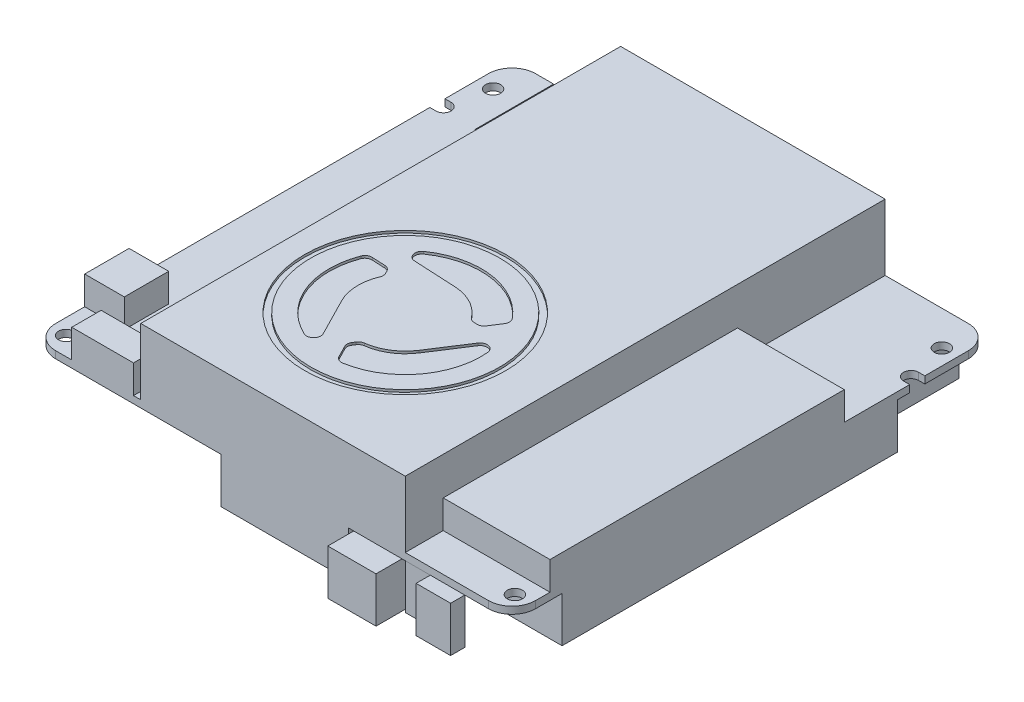
SolidWorks part; units mm, degrees
ref_plane "Спереди" through (0, 0, 0) normal (0, 0, 1) x (1, 0, 0)
ref_plane "Сверху" through (0, 0, 0) normal (0, 1, 0) x (1, 0, 0)
ref_plane "Справа" through (0, 0, 0) normal (1, 0, 0) x (0, 0, -1)
sketch "Эскиз1" plane through (0, 0, 0) normal (0, 1, 0) x (1, 0, 0)
  line L0 (-62.5901, -46.9) -> (98.0952, -46.9) construction
  line L1 (-45.8, 50.8) -> (-41.9874, 50.8)
  line L2 (-50.8, 45.8) -> (-50.8, -45.8)
  line L3 (-45.8, -50.8) -> (45.8, -50.8)
  line L4 (50.8, 45.8) -> (50.8, -45.8)
  line L5 (-50.8, 50.8) -> (50.8, -50.8) construction
  line L6 (-50.8, -50.8) -> (50.8, 50.8) construction
  line L7 (-47.5, 92.2985) -> (-47.5, -70.4765) construction
  line L8 (47.5, 92.2985) -> (47.5, -70.4765) construction
  line L9 (-85.2704, 43.5) -> (74.0758, 43.5) construction
  line L10 (-65.9548, 35) -> (74.0758, 35) construction
  line L11 (-49.5, 37.9623) -> (-49.5, 31.6688) construction
  line L12 (49.5, 37.9623) -> (49.5, 31.6688) construction
  line L13 (-28.7603, 50.8) -> (45.8, 50.8)
  line L14 (-49.5, 36.6) -> (-50.8, 36.6)
  line L16 (-49.5, 33.4) -> (-50.8, 33.4)
  line L17 (-50.8, 36.6) -> (-50.8, 33.4)
  line L18 (49.5, 36.6) -> (50.8, 36.6)
  line L19 (-28.7603, 50.8) -> (-28.7603, 34.1137)
  line L20 (49.5, 33.4) -> (50.8, 33.4)
  line L21 (50.8, 36.6) -> (50.8, 33.4)
  line L22 (-28.7603, 34.1137) -> (-41.9874, 34.1137)
  line L23 (-41.9874, 50.8) -> (-41.9874, 34.1137)
  arc A0 (45.8, 50.8) -> (50.8, 45.8) centre (45.8, 45.8) cw
  arc A1 (50.8, -45.8) -> (45.8, -50.8) centre (45.8, -45.8) cw
  arc A2 (-45.8, -50.8) -> (-50.8, -45.8) centre (-45.8, -45.8) cw
  arc A3 (-50.8, 45.8) -> (-45.8, 50.8) centre (-45.8, 45.8) cw
  circle A4 centre (-47.5, -46.9) radius 1.6
  circle A5 centre (47.5, -46.9) radius 1.6
  circle A6 centre (47.5, 43.5) radius 1.6
  circle A7 centre (-47.5, 43.5) radius 1.6
  arc A8 (-49.5, 33.4) -> (-49.5, 36.6) centre (-49.5, 35) ccw
  arc A9 (49.5, 36.6) -> (49.5, 33.4) centre (49.5, 35) ccw
  point P0 (0, 0)
  dimension "D3" = 5
  dimension "D8" = 3.2
  dimension "D9" = 8.5
  dimension "D1" = 101.6
  dimension "D2" = 101.6
  dimension "D4" = 3.3
  dimension "D5" = 95
  dimension "D6" = 7.3
  dimension "D7" = 90.4
  dimension "D10" = 1.3
  dimension "D11" = 99
extrude "Бобышка-Вытянуть1" add sketch "Эскиз1" along normal blind 1.5 contours A9 L18 L4 A0 L1 A3 L2 L14 A8 L16 A2 L3 A1 L20 A7 A6 A5 A4 region at (0.7783, 0, 0.9857)
sketch "Эскиз2" plane through (0, 1.5, 0) normal (0, 1, 0) x (1, 0, 0)
  line L0 (-45.8, 50.8) -> (-41.9874, 50.8) construction
  line L1 (-27.8, 50.8) -> (28.2, 50.8)
  line L2 (-27.8, 50.8) -> (-27.8, -50.8)
  line L3 (-27.8, -50.8) -> (28.2, -50.8)
  line L4 (28.2, 50.8) -> (28.2, -50.8)
  line L5 (-45.8, -50.8) -> (45.8, -50.8) construction
  dimension "D1" = 23
  dimension "D2" = 56
extrude "Бобышка-Вытянуть2" add sketch "Эскиз2" along normal blind 14
sketch "Эскиз3" plane through (0, 1.5, 0) normal (0, 1, 0) x (1, 0, 0)
  line L0 (28.2, -50.8) -> (28.2, 50.8) construction
  line L1 (28.2, 19.545) -> (50.8, 19.545)
  line L2 (28.2, 19.545) -> (28.2, -42.7592)
  line L3 (28.2, -42.7592) -> (50.8, -42.7592)
  line L4 (50.8, 19.545) -> (50.8, -42.7592)
  line L5 (50.8, 33.4) -> (50.8, -45.8) construction
  line L6 (-45.8, -50.8) -> (-27.8, -50.8) construction
  line L7 (-42.4088, -50.8) -> (-29.3358, -50.8)
  line L8 (-42.4088, -50.8) -> (-42.4088, -44.5816)
  line L9 (-42.4088, -44.5816) -> (-29.3358, -44.5816)
  line L10 (-29.3358, -50.8) -> (-29.3358, -44.5816)
  line L11 (-50.8, 33.4) -> (-50.8, -45.8) construction
  line L12 (-50.8, -39.6706) -> (-42.4088, -39.6706)
  line L13 (-50.8, -39.6706) -> (-50.8, -30.2711)
  line L14 (-50.8, -30.2711) -> (-42.4088, -30.2711)
  line L15 (-42.4088, -39.6706) -> (-42.4088, -30.2711)
extrude "Бобышка-Вытянуть3" add sketch "Эскиз3" along normal blind 6
sketch "Эскиз4" plane through (0, 0, 0) normal (0, -1, 0) x (1, 0, 0)
  line L0 (-45.8, -50.8) -> (-41.9874, -50.8) construction
  line L1 (30.8, -50.8) -> (24.8, -50.8)
  line L2 (30.8, -50.8) -> (30.8, -39.5)
  line L3 (30.8, -39.5) -> (24.8, -39.5)
  line L4 (24.8, -50.8) -> (24.8, -39.5)
  line L5 (50.8, -45.8) -> (50.8, -36.6) construction
  dimension "D1" = 20
  dimension "D2" = 11.3
  dimension "D3" = 6
extrude "Бобышка-Вытянуть4" add sketch "Эскиз4" along normal blind 13.4
sketch "Эскиз5" plane through (0, 0, -50.8) normal (0, 0, -1) x (-1, 0, 0)
  line L0 (-28.2, 15.5) -> (27.8, 15.5) construction
  line L1 (-27.4063, 15.4) -> (-25.6563, 15.4)
  line L2 (-27.4063, 15.4) -> (-27.4063, 7.4)
  line L3 (-27.4063, 7.4) -> (-25.6563, 7.4)
  line L4 (-25.6563, 15.4) -> (-25.6563, 7.4)
  line L5 (-25.4563, 15.4) -> (-23.7063, 15.4)
  line L6 (-25.4563, 15.4) -> (-25.4563, 7.4)
  line L7 (-25.4563, 7.4) -> (-23.7063, 7.4)
  line L8 (-23.7063, 15.4) -> (-23.7063, 7.4)
  line L9 (-23.5063, 15.4) -> (-21.7563, 15.4)
  line L10 (-23.5063, 15.4) -> (-23.5063, 7.4)
  line L11 (-23.5063, 7.4) -> (-21.7563, 7.4)
  line L12 (-21.7563, 15.4) -> (-21.7563, 7.4)
  line L13 (-21.5563, 15.4) -> (-19.8063, 15.4)
  line L14 (-21.5563, 15.4) -> (-21.5563, 7.4)
  line L15 (-21.5563, 7.4) -> (-19.8063, 7.4)
  line L16 (-19.8063, 15.4) -> (-19.8063, 7.4)
  line L17 (-19.6063, 15.4) -> (-17.8563, 15.4)
  line L18 (-19.6063, 15.4) -> (-19.6063, 7.4)
  line L19 (-19.6063, 7.4) -> (-17.8563, 7.4)
  line L20 (-17.8563, 15.4) -> (-17.8563, 7.4)
  line L21 (-17.6563, 15.4) -> (-15.9063, 15.4)
  line L22 (-17.6563, 15.4) -> (-17.6563, 7.4)
  line L23 (-17.6563, 7.4) -> (-15.9063, 7.4)
  line L24 (-15.9063, 15.4) -> (-15.9063, 7.4)
  line L25 (-15.7063, 15.4) -> (-13.9563, 15.4)
  line L26 (-15.7063, 15.4) -> (-15.7063, 7.4)
  line L27 (-15.7063, 7.4) -> (-13.9563, 7.4)
  line L28 (-13.9563, 15.4) -> (-13.9563, 7.4)
  line L29 (-13.7563, 15.4) -> (-12.0063, 15.4)
  line L30 (-13.7563, 15.4) -> (-13.7563, 7.4)
  line L31 (-13.7563, 7.4) -> (-12.0063, 7.4)
  line L32 (-12.0063, 15.4) -> (-12.0063, 7.4)
  line L33 (-11.8063, 15.4) -> (-10.0563, 15.4)
  line L34 (-11.8063, 15.4) -> (-11.8063, 7.4)
  line L35 (-11.8063, 7.4) -> (-10.0563, 7.4)
  line L36 (-10.0563, 15.4) -> (-10.0563, 7.4)
  line L37 (-9.8563, 15.4) -> (-8.1063, 15.4)
  line L38 (-9.8563, 15.4) -> (-9.8563, 7.4)
  line L39 (-9.8563, 7.4) -> (-8.1063, 7.4)
  line L40 (-8.1063, 15.4) -> (-8.1063, 7.4)
  line L41 (-7.9063, 15.4) -> (-6.1563, 15.4)
  line L42 (-7.9063, 15.4) -> (-7.9063, 7.4)
  line L43 (-7.9063, 7.4) -> (-6.1563, 7.4)
  line L44 (-6.1563, 15.4) -> (-6.1563, 7.4)
  line L45 (-5.9563, 15.4) -> (-4.2063, 15.4)
  line L46 (-5.9563, 15.4) -> (-5.9563, 7.4)
  line L47 (-5.9563, 7.4) -> (-4.2063, 7.4)
  line L48 (-4.2063, 15.4) -> (-4.2063, 7.4)
  line L49 (-4.0063, 15.4) -> (-2.2563, 15.4)
  line L50 (-4.0063, 15.4) -> (-4.0063, 7.4)
  line L51 (-4.0063, 7.4) -> (-2.2563, 7.4)
  line L52 (-2.2563, 15.4) -> (-2.2563, 7.4)
  line L53 (-2.0563, 15.4) -> (-0.3063, 15.4)
  line L54 (-2.0563, 15.4) -> (-2.0563, 7.4)
  line L55 (-2.0563, 7.4) -> (-0.3063, 7.4)
  line L56 (-0.3063, 15.4) -> (-0.3063, 7.4)
  line L57 (-0.1063, 15.4) -> (1.6437, 15.4)
  line L58 (-0.1063, 15.4) -> (-0.1063, 7.4)
  line L59 (-0.1063, 7.4) -> (1.6437, 7.4)
  line L60 (1.6437, 15.4) -> (1.6437, 7.4)
  line L61 (1.8437, 15.4) -> (3.5937, 15.4)
  line L62 (1.8437, 15.4) -> (1.8437, 7.4)
  line L63 (1.8437, 7.4) -> (3.5937, 7.4)
  line L64 (3.5937, 15.4) -> (3.5937, 7.4)
  line L65 (3.7937, 15.4) -> (5.5437, 15.4)
  line L66 (3.7937, 15.4) -> (3.7937, 7.4)
  line L67 (3.7937, 7.4) -> (5.5437, 7.4)
  line L68 (5.5437, 15.4) -> (5.5437, 7.4)
  line L69 (5.7437, 15.4) -> (7.4937, 15.4)
  line L70 (5.7437, 15.4) -> (5.7437, 7.4)
  line L71 (5.7437, 7.4) -> (7.4937, 7.4)
  line L72 (7.4937, 15.4) -> (7.4937, 7.4)
  line L73 (7.6937, 15.4) -> (9.4437, 15.4)
  line L74 (7.6937, 15.4) -> (7.6937, 7.4)
  line L75 (7.6937, 7.4) -> (9.4437, 7.4)
  line L76 (9.4437, 15.4) -> (9.4437, 7.4)
  line L77 (9.6437, 15.4) -> (11.3937, 15.4)
  line L78 (9.6437, 15.4) -> (9.6437, 7.4)
  line L79 (9.6437, 7.4) -> (11.3937, 7.4)
  line L80 (11.3937, 15.4) -> (11.3937, 7.4)
  line L81 (11.5937, 15.4) -> (13.3437, 15.4)
  line L82 (11.5937, 15.4) -> (11.5937, 7.4)
  line L83 (11.5937, 7.4) -> (13.3437, 7.4)
  line L84 (13.3437, 15.4) -> (13.3437, 7.4)
  line L85 (13.5437, 15.4) -> (15.2937, 15.4)
  line L86 (13.5437, 15.4) -> (13.5437, 7.4)
  line L87 (13.5437, 7.4) -> (15.2937, 7.4)
  line L88 (15.2937, 15.4) -> (15.2937, 7.4)
  line L89 (15.4937, 15.4) -> (17.2437, 15.4)
  line L90 (15.4937, 15.4) -> (15.4937, 7.4)
  line L91 (15.4937, 7.4) -> (17.2437, 7.4)
  line L92 (17.2437, 15.4) -> (17.2437, 7.4)
  line L93 (17.4437, 15.4) -> (19.1937, 15.4)
  line L94 (17.4437, 15.4) -> (17.4437, 7.4)
  line L95 (17.4437, 7.4) -> (19.1937, 7.4)
  line L96 (19.1937, 15.4) -> (19.1937, 7.4)
  line L97 (19.3937, 15.4) -> (21.1437, 15.4)
  line L98 (19.3937, 15.4) -> (19.3937, 7.4)
  line L99 (19.3937, 7.4) -> (21.1437, 7.4)
  line L100 (21.1437, 15.4) -> (21.1437, 7.4)
  line L101 (21.3437, 15.4) -> (23.0937, 15.4)
  line L102 (21.3437, 15.4) -> (21.3437, 7.4)
  line L103 (21.3437, 7.4) -> (23.0937, 7.4)
  line L104 (23.0937, 15.4) -> (23.0937, 7.4)
  line L105 (23.2937, 15.4) -> (25.0437, 15.4)
  line L106 (23.2937, 15.4) -> (23.2937, 7.4)
  line L107 (23.2937, 7.4) -> (25.0437, 7.4)
  line L108 (25.0437, 15.4) -> (25.0437, 7.4)
  line L109 (25.2437, 15.4) -> (26.9937, 15.4)
  line L110 (25.2437, 15.4) -> (25.2437, 7.4)
  line L111 (25.2437, 7.4) -> (26.9937, 7.4)
  line L112 (26.9937, 15.4) -> (26.9937, 7.4)
  dimension "D1" = 1.75
  dimension "D2" = 8
  dimension "D3" = 0.1
  dimension "D5" = 28
extrude "Вырез-Вытянуть1" cut sketch "Эскиз5" against normal blind 45
sketch "Эскиз6" plane through (0, 0, 0) normal (0, -1, 0) x (1, 0, 0)
  line L0 (-45.8, -50.8) -> (-41.9874, -50.8) construction
  line L1 (43.8, -50.8) -> (23.8, -50.8)
  line L2 (43.8, -50.8) -> (43.8, -37.8)
  line L3 (43.8, -37.8) -> (23.8, -37.8)
  line L4 (23.8, -50.8) -> (23.8, -37.8)
  line L5 (50.8, -45.8) -> (50.8, -36.6) construction
  line L6 (-45.8, -50.8) -> (-41.9874, -50.8) construction
  line L7 (-26.8, -50.8) -> (-5.8, -50.8)
  line L8 (-26.8, -50.8) -> (-26.8, -26.8)
  line L9 (-26.8, -26.8) -> (-5.8, -26.8)
  line L10 (-5.8, -50.8) -> (-5.8, -26.8)
  line L11 (-50.8, -45.8) -> (-50.8, -36.6) construction
  line L12 (-50.8, -33.4) -> (-50.8, 45.8) construction
  line L13 (-50.8, -22.8) -> (-20.8, -22.8)
  line L14 (-50.8, -22.8) -> (-50.8, 32.2)
  line L15 (-50.8, 32.2) -> (-20.8, 32.2)
  line L16 (-20.8, -22.8) -> (-20.8, 32.2)
  line L17 (50.8, -33.4) -> (50.8, 45.8) construction
  line L18 (50.8, -30.8) -> (-0.2, -30.8)
  line L19 (50.8, -30.8) -> (50.8, 40.2)
  line L20 (50.8, 40.2) -> (-0.2, 40.2)
  line L21 (-0.2, -30.8) -> (-0.2, 40.2)
  line L22 (-45.8, 50.8) -> (45.8, 50.8) construction
  line L28 (-3.8, 24.8) -> (-10.16, 24.8)
  line L29 (-3.8, 24.8) -> (-3.8, 40.8)
  line L30 (-3.8, 40.8) -> (-10.16, 40.8)
  line L31 (-10.16, 24.8) -> (-10.16, 40.8)
  line L32 (-10.8, 50.8) -> (16.2, 50.8)
  line L33 (-10.8, 50.8) -> (-10.8, 46.8)
  line L34 (-10.8, 46.8) -> (16.2, 46.8)
  line L35 (16.2, 50.8) -> (16.2, 46.8)
  line L36 (27.51, 42.8) -> (17.3, 42.8)
  line L37 (27.51, 42.8) -> (27.51, 56.3)
  line L38 (27.51, 56.3) -> (17.3, 56.3)
  line L39 (17.3, 42.8) -> (17.3, 56.3)
  line L40 (35.8, 48.2) -> (28.2, 48.2)
  line L41 (35.8, 48.2) -> (35.8, 50.7)
  line L42 (35.8, 50.7) -> (28.2, 50.7)
  line L43 (28.2, 48.2) -> (28.2, 50.7)
  line L44 (40.8, 50.8) -> (33.5, 50.8)
  line L45 (40.8, 50.8) -> (40.8, 53.8)
  line L46 (40.8, 53.8) -> (33.5, 53.8)
  line L47 (33.5, 50.8) -> (33.5, 53.8)
  dimension "D1" = 7
  dimension "D2" = 20
  dimension "D3" = 13
  dimension "D4" = 24
  dimension "D5" = 21
  dimension "D6" = 24
  dimension "D7" = 28
  dimension "D8" = 55
  dimension "D9" = 30
  dimension "D10" = 51
  dimension "D11" = 20
  dimension "D12" = 71
  dimension "D17" = 16
  dimension "D18" = 6.36
  dimension "D20" = 47
  dimension "D21" = 27
  dimension "D23" = 40
  dimension "D24" = 3
  dimension "D25" = 7.3
  dimension "D26" = 10
  dimension "D27" = 0
  dimension "D28" = 7.6
  dimension "D29" = 2.5
  dimension "D30" = 0.1
  dimension "D31" = 15
  dimension "D32" = 33.5
  dimension "D33" = 10.21
  dimension "D34" = 13.5
  dimension "D35" = 5.5
extrude "Бобышка-Вытянуть5" add sketch "Эскиз6" along normal blind 9.6
sketch "Эскиз7" plane through (0, 15.5, 0) normal (0, 1, 0) x (1, 0, 0)
  line L0 (-12.6168, -14.3143) -> (-15.3932, -14.1729)
  line L1 (-27.8, -50.8) -> (28.2, -50.8) construction
  line L2 (28.2, -50.8) -> (28.2, 50.8) construction
  line L3 (10.7358, -12.3415) -> (9.2252, -14.6753)
  line L4 (-1.2916, -10.8129) -> (-10.2749, -10.3556)
  line L5 (-10.7033, -25.3532) -> (-6.6076, -33.3617)
  line L6 (6.5948, -26.2338) -> (11.4826, -18.6827)
  line L7 (7.8897, -15.3582) -> (7.2698, -15.3267)
  line L8 (-11.3576, -15.1294) -> (-11.0749, -15.682)
  line L9 (-2.0084, -33.4105) -> (-0.7426, -35.8856)
  line L10 (-1.5948, -31.3913) -> (-1.9321, -31.9124)
  circle A0 centre (-1.8, -20.8) radius 20
  circle A1 centre (-1.8, -20.8) radius 21.3
  arc A2 (6.5449, -15.2898) -> (-1.2916, -10.8129) centre (-1.8, -20.8) ccw construction
  arc A3 (10.6351, -10.5737) -> (-11.0616, -7.6306) centre (-1.8, -20.8) ccw
  arc A4 (6.1531, -14.7379) -> (-1.2916, -10.8129) centre (-1.8, -20.8) ccw
  arc A5 (-11.0264, -16.9435) -> (-10.7033, -25.3532) centre (-1.8, -20.8) ccw
  arc A6 (-10.7444, -16.3282) -> (-10.7033, -25.3532) centre (-1.8, -20.8) ccw construction
  arc A7 (-0.5266, -30.7186) -> (6.5948, -26.2338) centre (-1.8, -20.8) ccw
  arc A8 (-1.2005, -30.782) -> (6.5948, -26.2338) centre (-1.8, -20.8) ccw construction
  circle A9 centre (-1.8, -20.8) radius 16.1 construction
  arc A10 (0.8387, -36.6823) -> (14.2358, -19.364) centre (-1.8, -20.8) ccw
  arc A11 (-16.8738, -15.144) -> (-8.5743, -35.4054) centre (-1.8, -20.8) ccw
  arc A12 (14.2358, -19.364) -> (11.4826, -18.6827) centre (12.7418, -19.4978) ccw
  arc A13 (-10.2749, -10.3556) -> (-11.0616, -7.6306) centre (-10.1987, -8.8575) cw
  arc A14 (-8.5743, -35.4054) -> (-6.6076, -33.3617) centre (-7.9431, -34.0447) ccw
  arc A15 (-16.8738, -15.144) -> (-15.3932, -14.1729) centre (-15.4694, -15.671) cw
  arc A16 (-12.6168, -14.3143) -> (-11.3576, -15.1294) centre (-12.693, -15.8123) cw
  arc A17 (-11.0749, -15.682) -> (-11.0264, -16.9435) centre (-12.4104, -16.365) cw
  arc A18 (-0.7426, -35.8856) -> (0.8387, -36.6823) centre (0.5929, -35.2026) ccw
  arc A19 (-1.9321, -31.9124) -> (-2.0084, -33.4105) centre (-0.6729, -32.7275) ccw
  arc A20 (-1.5948, -31.3913) -> (-0.5266, -30.7186) centre (-0.3356, -32.2064) cw
  arc A21 (7.2698, -15.3267) -> (6.1531, -14.7379) centre (7.346, -13.8286) cw
  arc A22 (7.8897, -15.3582) -> (9.2252, -14.6753) centre (7.966, -13.8602) ccw
  arc A23 (10.7358, -12.3415) -> (10.6351, -10.5737) centre (9.4766, -11.5264) ccw
  point P33 (-16.4485, -14.1192)
  point P36 (-11.7519, -14.3583)
  point P42 (-0.2615, -36.8263)
  point P45 (-2.4027, -32.6394)
  dimension "D1" = 40
  dimension "D2" = 30
  dimension "D6" = 1.5
  dimension "D7" = 1.5
  dimension "D8" = 1.5
  dimension "D9" = 1.5
  dimension "D3" = 30
  dimension "D4" = 1.3
  dimension "D5" = 3.9
extrude "Вырез-Вытянуть2" cut sketch "Эскиз7" against normal blind 0.5 contours A1 A0 | L3 A23 A3 A13 L4 A4 A21 L7 A22 | A20 L10 A19 L9 A18 A10 A12 L6 A7 | A17 L8 A16 L0 A15 A11 A14 L5 A5 region at (-13.1051, 15.5, 24.5982) region at (0.5632, 15.5, 9.1104) region at (7.1419, 15.5, 28.6914) region at (-22.4975, 15.5, 20.8)
